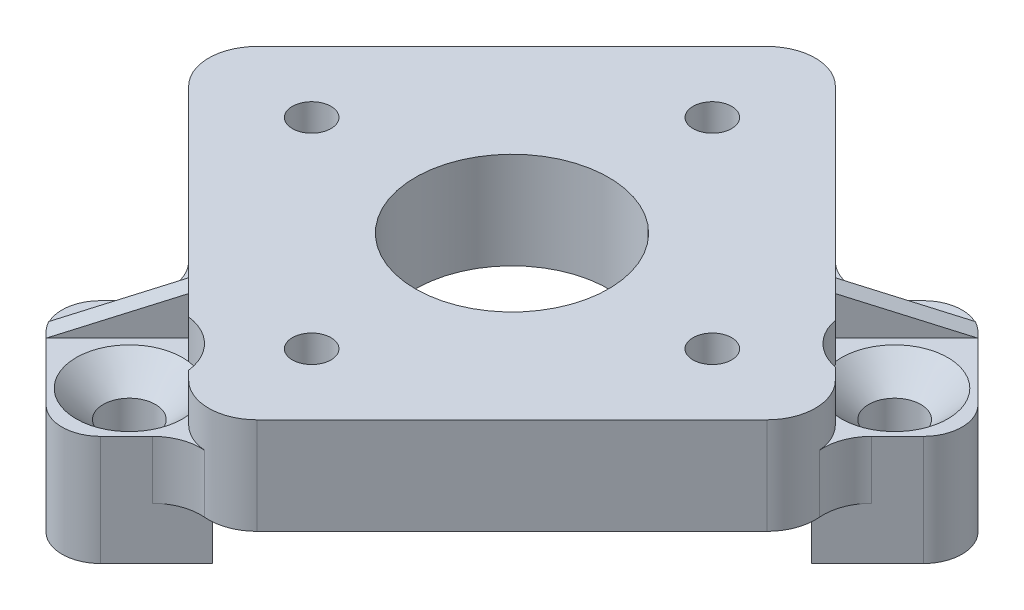
SolidWorks part; units mm, degrees
ref_plane "Front Plane" through (0, 0, 0) normal (0, 0, 1) x (1, 0, 0)
ref_plane "Top Plane" through (0, 0, 0) normal (0, 1, 0) x (1, 0, 0)
ref_plane "Right Plane" through (0, 0, 0) normal (1, 0, 0) x (0, 0, -1)
sketch "Sketch1" plane through (0, 0, 0) normal (0, 1, 0) x (1, 0, 0)
  line L0 (0, 10.365) -> (0, -10.365) construction
  line L1 (10.365, 0) -> (-10.365, 0) construction
  line L2 (0, 10.365) -> (10.365, 0) construction
  line L3 (10.365, 0) -> (0, -10.365) construction
  line L4 (0, -10.365) -> (-10.365, 0) construction
  line L8 (-10.365, 0) -> (0, 10.365) construction
  line L9 (1.7678, 14.9612) -> (14.9612, 1.7678)
  line L10 (14.9612, -1.7678) -> (1.7678, -14.9612)
  line L11 (-1.7678, -14.9612) -> (-14.9612, -1.7678)
  line L12 (-14.9612, 1.7678) -> (-1.7678, 14.9612)
  line L13 (16.729, 0) -> (0, -16.729) construction
  line L14 (0, -16.729) -> (-16.729, 0) construction
  line L15 (0, 16.729) -> (16.729, 0) construction
  line L16 (-16.729, 0) -> (0, 16.729) construction
  circle A7 centre (0, 10.365) radius 0.5
  circle A8 centre (0, -10.365) radius 0.5
  circle A9 centre (10.365, 0) radius 0.5
  circle A10 centre (-10.365, 0) radius 0.5
  circle A11 centre (0, 0) radius 5
  arc A12 (1.7678, -14.9612) -> (-1.7678, -14.9612) centre (0, -13.1934) cw
  arc A13 (14.9612, 1.7678) -> (14.9612, -1.7678) centre (13.1934, 0) cw
  arc A14 (-14.9612, -1.7678) -> (-14.9612, 1.7678) centre (-13.1934, 0) cw
  arc A15 (1.7678, 14.9612) -> (-1.7678, 14.9612) centre (0, 13.1934) ccw
  dimension "D2" = 1
  dimension "D3" = 10
  dimension "D4" = 4.5
  dimension "D5" = 2.5
  dimension "D1" = 20.73
extrude "Boss-Extrude1" add sketch "Sketch1" along normal blind 5
sketch "Sketch4" plane through (0, 0, 0) normal (0, -1, 0) x (1, 0, 0)
  circle A0 centre (0, 10.365) radius 3
  circle A1 centre (10.365, 0) radius 3
  circle A2 centre (-10.365, 0) radius 3
  circle A3 centre (0, -10.365) radius 3
  point P0 (0, 10.365)
  point P3 (10.365, 0)
  point P6 (-10.365, 0)
  point P9 (0, -10.365)
  dimension "D1" = 6
ref_plane "Plane1" through (0, -2.7, 0) normal (0, 1, 0) x (1, 0, 0)
ref_plane "Plane2" through (8.3645, 0, 8.3645) normal (0.7071, 0, 0.7071) x (0.7071, 0, -0.7071)
ref_plane "Plane3" through (2.7076, 0, 2.7076) normal (0.7071, 0, 0.7071) x (0.7071, 0, -0.7071)
sketch "Sketch3" plane through (0, -2.7, 0) normal (0, 1, 0) x (1, 0, 0)
  line L0 (-8.3645, 8.3645) -> (8.3645, -8.3645) construction
  line L1 (-1.7678, 14.9612) -> (-14.9612, 1.7678) construction
  line L2 (1.7678, -14.9612) -> (14.9612, -1.7678) construction
  line L3 (9.8995, 9.8995) -> (14.8492, 4.9497) construction
  line L5 (10.5375, 4.9497) -> (14.8492, 0.638)
  line L12 (14.9612, 1.7678) -> (1.7678, 14.9612) construction
  line L13 (14.8492, 0.638) -> (19.161, 4.9497)
  line L20 (0, 0) -> (9.8995, 9.8995) construction
  line L21 (14.9612, 1.7678) -> (1.7678, 14.9612) construction
  line L22 (19.161, 4.9497) -> (14.8492, 9.2615)
  line L23 (14.8492, 9.2615) -> (10.5375, 4.9497)
  line L24 (19.161, 4.9497) -> (10.5375, 4.9497) construction
  line L25 (-4.9497, -19.161) -> (-4.9497, -10.5375) construction
  line L26 (-9.8995, -9.8995) -> (-4.9497, -14.8492) construction
  line L27 (-9.2615, -14.8492) -> (-4.9497, -10.5375)
  line L28 (-4.9497, -19.161) -> (-9.2615, -14.8492)
  line L29 (-0.638, -14.8492) -> (-4.9497, -19.161)
  line L30 (-4.9497, -10.5375) -> (-0.638, -14.8492)
  line L31 (10.5375, 4.9497) -> (8.7697, 6.7175)
  line L32 (8.7697, 6.7175) -> (13.0815, 11.0293)
  line L33 (13.0815, 11.0293) -> (14.8492, 9.2615)
  line L34 (-4.9497, -10.5375) -> (-6.7175, -8.7697)
  line L35 (-6.7175, -8.7697) -> (-11.0293, -13.0815)
  line L36 (-11.0293, -13.0815) -> (-9.2615, -14.8492)
  circle A2 centre (14.8492, 4.9497) radius 1.3
  circle A3 centre (-4.9497, -14.8492) radius 1.3
  dimension "D1" = 2.6
  dimension "D2" = 7
  dimension "D3" = 3.0489
  dimension "D4" = 14
  dimension "D5" = 2.5
extrude "Boss-Extrude4" add sketch "Sketch3" along normal offset from surface (5.7 mm away) 3 contours L30 L27 L28 L29 A3 | L35 L36 L27 L34 | L22 L23 L5 L13 A2 | L33 L32 L31 L23 region at (12.7796, -2.7, -7.0194) region at (11.8095, -2.7, -7.9895) region at (-7.9895, -2.7, 11.8095) region at (-7.0194, -2.7, 12.7796) up to face at (-10.365, 0, 0.5)
sketch "Sketch7" plane through (2.7076, 0, 2.7076) normal (0.7071, 0, 0.7071) x (0.7071, 0, -0.7071)
  line L0 (11.8292, 5) -> (17.0489, 3)
  line L1 (-11.8292, 5) -> (-17.0489, 3)
  line L2 (-17.0489, 3) -> (-11.8292, 3)
  line L3 (-11.8292, 3) -> (-11.8292, 5)
  line L4 (11.8292, 5) -> (11.8292, 3)
  line L5 (11.8292, 3) -> (17.0489, 3)
extrude "Boss-Extrude6" add sketch "Sketch7" against normal blind 1
fillet "Fillet1" radius 2.5 4 edges at (-7.3384, 1.5, 9.3906) (9.3906, 1.5, -7.3384) (15.3953, 1.5, -1.184) (-1.184, 1.5, 15.3953)
fillet "Fillet2" radius 2 4 edges at (-11.0293, 0.15, 13.0815) (-4.9497, 0.15, 19.161) (13.0815, 0.15, -11.0293) (19.161, 0.15, -4.9497)
hole_wizard "Ø2.0mm Dowel Hole1" positions "Sketch4" profile "Sketch11" hole size "Ø2.0" standard "ANSI Metric"
sketch "Sketch11" plane through (0, 0, 10.365) normal (1, 0, 0) x (0, 0, -1)
  line L0 (0, 0) -> (0, 43.5309)
  line L1 (0, 43.5309) -> (1, 42.93)
  line L2 (1, 42.93) -> (1, 0)
  line L5 (1, 0) -> (0, 0)
  line L10 (0, 43.5309) -> (-1, 42.93) construction
  line L11 (0, -6.35) -> (0, 107.95) construction
  dimension "Hole Dia." = 2
  dimension "Hole Depth" = 42.93
  dimension "Drill Angle" = 118
sketch "Sketch12" plane through (0, 3, 0) normal (0, 1, 0) x (1, 0, 0)
  circle A0 centre (-4.9497, -14.8492) radius 2.75
  circle A1 centre (14.8492, 4.9497) radius 2.625
  dimension "D1" = 5.5
  dimension "D2" = 5.25
extrude "Cut-Extrude1" cut sketch "Sketch12" along normal blind 10
hole_wizard "CSK for M2.5 Flat Head Machine Screw1" positions "3DSketch1" profile "Sketch13" countersink size "M2.5" standard "ANSI Metric"
sketch3d "3DSketch1"
  line L0 (-4.9497, 3, 14.8492) -> (-4.9497, -2.7, 14.8492) construction
  line L1 (14.8492, 3, -4.9497) -> (14.8492, -2.7, -4.9497) construction
  point P0 (-4.9497, 3, 14.8492)
  point P4 (14.8492, 3, -4.9497)
sketch "Sketch13" plane through (-4.9497, 3, 14.8492) normal (1, 0, 0) x (0, 0, 1)
  line L0 (0, 0) -> (0, 43.7412)
  line L1 (0, 43.7412) -> (1.35, 42.93)
  line L2 (1.35, 42.93) -> (1.35, 1.4)
  line L3 (1.35, 1.4) -> (2.75, 0)
  line L5 (2.75, 0) -> (0, 0)
  line L6 (-1.35, 1.4) -> (-2.75, 0) construction
  line L10 (0, 43.7412) -> (-1.35, 42.93) construction
  line L11 (0, -6.35) -> (0, 107.95) construction
  dimension "Hole Dia." = 2.7
  dimension "Hole Depth" = 42.93
  dimension "Near C'Sink Dia." = 5.5
  dimension "Near C'Sink Angle" = 90
  dimension "Drill Angle" = 118
